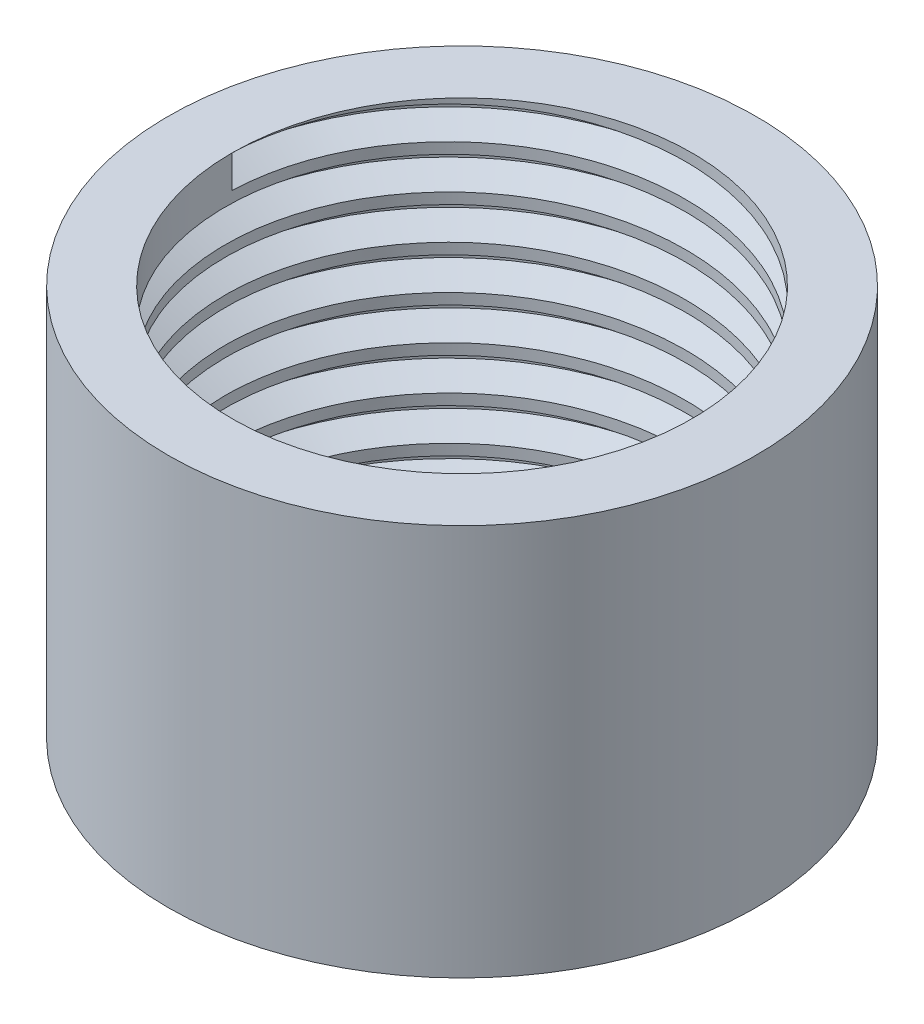
SolidWorks part; units mm, degrees
ref_plane "Front Plane" through (0, 0, 0) normal (0, 0, 1) x (1, 0, 0)
ref_plane "Top Plane" through (0, 0, 0) normal (0, 1, 0) x (1, 0, 0)
ref_plane "Right Plane" through (0, 0, 0) normal (1, 0, 0) x (0, 0, -1)
sketch "Sketch1" plane through (0, 0, 0) normal (0, 1, 0) x (1, 0, 0)
  circle A0 centre (0, 0) radius 7.4612
  circle A1 centre (0, 0) radius 9.525
  dimension "D1" = 14.9225
  dimension "D2" = 19.05
extrude "Boss-Extrude1" add sketch "Sketch1" along normal blind 12.7 contours A1 A0 region at (-9.2556, 0, 0)
thread "Thread1" pitch 1.4111 method cut profile "Thread Profile1" start angle 0, offset 0, length 0, pitch 1.4111, diameter 14.9225
ref_plane "Plane1" through (-7.4612, 12.7, 0) normal (0, 0, 1) x (-1, 0, 0)
sketch "Thread Profile1" plane through (-7.4612, 12.7, 0) normal (0, 0, 1) x (-1, 0, 0)
  line L0 (0, 0) -> (0, 1.4111) construction
  line L1 (0, 0) -> (0.7638, 0.441)
  line L2 (0.7638, 0.441) -> (0.7638, 0.6174)
  line L3 (0.7638, 0.6174) -> (0, 1.0583)
  line L4 (0.7638, 0.5292) -> (0, 0.5292) construction
  line L11 (0, 0) -> (0, 1.0583)
  point P2 (0, 0)
  dimension "Pitch" = 1.4111
  dimension "Profile_Angle" = 60
  dimension "Profile_Land" = 0.1764
  dimension "Profile_Height" = 0.7638
